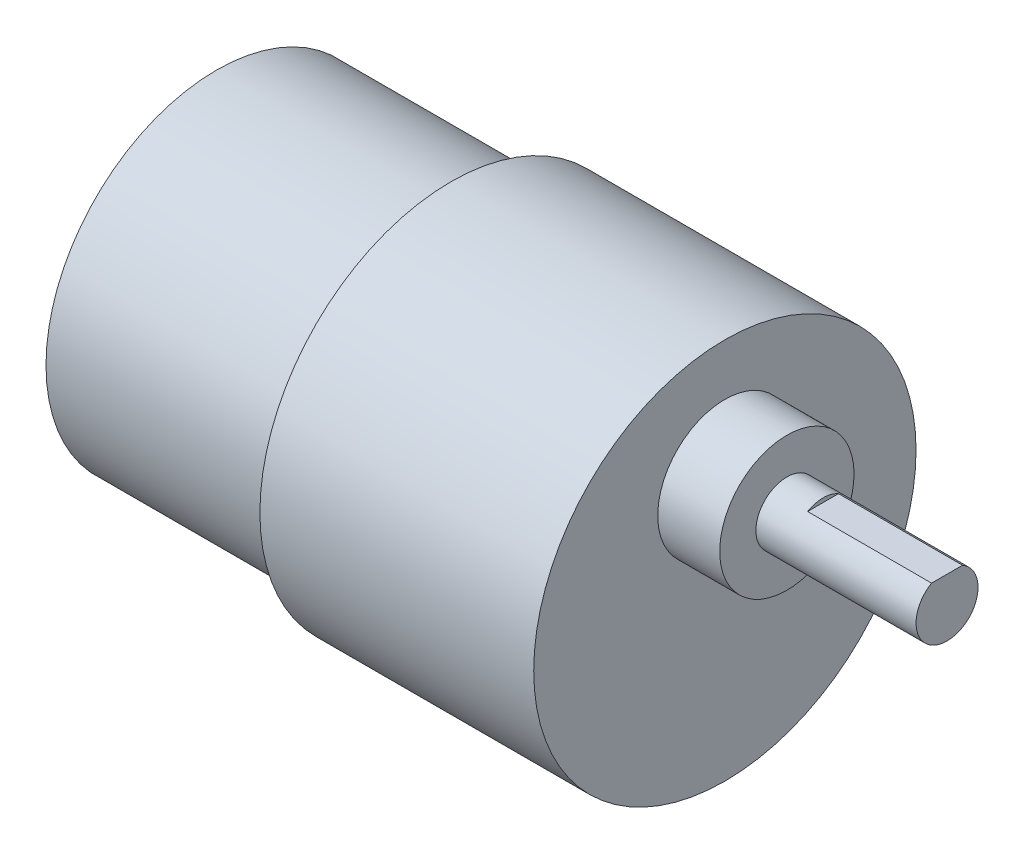
SolidWorks part; units mm, degrees
ref_plane "前视基准面" through (0, 0, 0) normal (0, 0, 1) x (1, 0, 0)
ref_plane "上视基准面" through (0, 0, 0) normal (0, 1, 0) x (1, 0, 0)
ref_plane "右视基准面" through (0, 0, 0) normal (1, 0, 0) x (0, 0, -1)
sketch "草图1" plane through (0, 0, 0) normal (1, 0, 0) x (0, 0, -1)
  circle A0 centre (0, 0) radius 16.5
  dimension "D1" = 33
extrude "凸台-拉伸1" add sketch "草图1" along normal blind 22.7
sketch "草图2" plane through (22.7, 0, 0) normal (1, 0, 0) x (0, 0, -1)
  circle A0 centre (0, 0) radius 18.5
  dimension "D1" = 37
extrude "凸台-拉伸2" add sketch "草图2" along normal blind 24
sketch "草图3" plane through (46.7, 0, 0) normal (1, 0, 0) x (0, 0, -1)
  circle A0 centre (0, 7) radius 6.5
  dimension "D2" = 13
  dimension "D1" = 7
extrude "凸台-拉伸3" add sketch "草图3" along normal blind 8.5
sketch "草图4" plane through (55.2, 0, 0) normal (1, 0, 0) x (0, 0, -1)
  circle A0 centre (0, 7) radius 3
  dimension "D1" = 6
sketch "草图5" plane through (46.7, 0, 0) normal (1, 0, 0) x (0, 0, -1)
  circle A0 centre (0, 0) radius 15.5 construction
  circle A1 centre (-15.5, 0) radius 1.5
  circle A2 centre (-7.75, 13.4234) radius 1.5
  circle A3 centre (7.75, 13.4234) radius 1.5
  circle A4 centre (15.5, 0) radius 1.5
  circle A5 centre (7.75, -13.4234) radius 1.5
  circle A6 centre (-7.75, -13.4234) radius 1.5
  dimension "D1" = 31
  dimension "D2" = 3
  dimension "D3" = 6
extrude "切除-拉伸2" cut sketch "草图5" against normal blind 10
extrude "凸台-拉伸4" add sketch "草图2<2>" along normal blind 26.5
sketch "草图2<2>" plane through (22.7, 0, 0) normal (1, 0, 0) x (0, 0, -1) same geometry as "草图2"
extrude "凸台-拉伸5" add sketch "草图3<2>" along normal blind 6
sketch "草图3<2>" plane through (46.7, 0, 0) normal (1, 0, 0) x (0, 0, -1) same geometry as "草图3"
sketch "草图9" plane through (55.2, 0, 0) normal (1, 0, 0) x (0, 0, -1)
  circle A0 centre (0, 7) radius 3
extrude "凸台-拉伸6" add sketch "草图9" along normal blind 15.5
sketch "草图10" plane through (70.7, 0, 0) normal (1, 0, 0) x (0, 0, -1)
  line L2 (-1.4967, 9.6) -> (1.4967, 9.6)
  circle A0 centre (0, 7) radius 3 construction
extrude "切除-拉伸3" cut sketch "草图10" against normal blind 12 and the other way through all
sketch "草图11" plane through (0, 0, 0) normal (-1, 0, 0) x (0, 0, 1)
  circle A0 centre (0, 0) radius 6
  dimension "D1" = 12
extrude "凸台-拉伸7" add sketch "草图11" along normal blind 2
fillet "圆角1" radius 0.5 1 edges at (-2, 0, 6)
